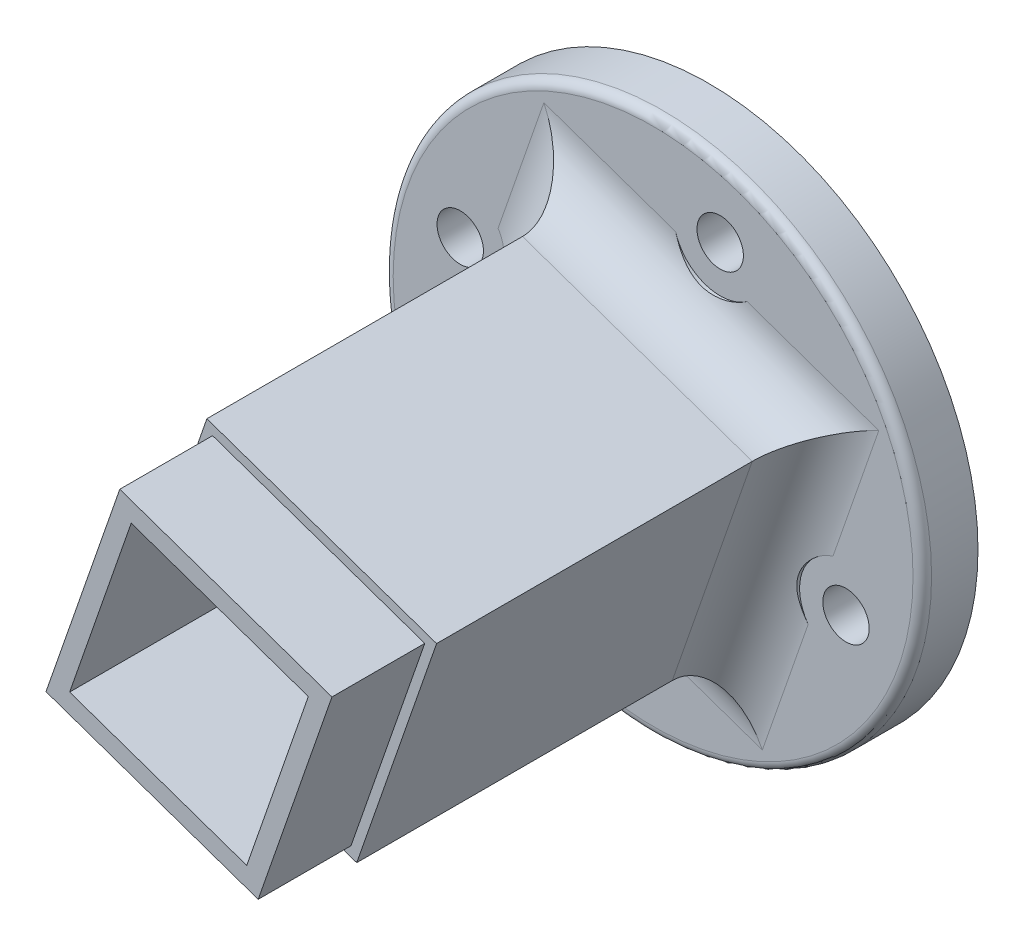
SolidWorks part; units mm, degrees
ref_plane "前视基准面" through (0, 0, 0) normal (0, 0, 1) x (1, 0, 0)
ref_plane "上视基准面" through (0, 0, 0) normal (0, 1, 0) x (1, 0, 0)
ref_plane "右视基准面" through (0, 0, 0) normal (1, 0, 0) x (0, 0, -1)
sketch "草图1" plane through (0, 0, 0) normal (0, 0, 1) x (1, 0, 0)
  line L0 (1.9417, -4.0121) -> (-2.8502, 5.8893) construction
  line L1 (1.9417, -4.0121) -> (5.5546, 6.3777) construction
  circle A0 centre (-2.8502, 5.8893) radius 1.25
  circle A1 centre (5.5546, 6.3777) radius 1.25
  circle A2 centre (11.8431, 0.7799) radius 1.25
  circle A3 centre (12.3314, -7.625) radius 1.25
  circle A4 centre (6.7336, -13.9134) radius 1.25
  circle A5 centre (-1.6712, -14.4018) radius 1.25
  circle A6 centre (-7.9597, -8.804) radius 1.25
  circle A7 centre (-8.448, -0.3991) radius 1.25
  circle A8 centre (1.9417, -4.0121) radius 14.5
  dimension "D1" = 2.5
  dimension "D3" = 29
  dimension "D2" = 45
extrude "凸台-拉伸1" add sketch "草图1" along normal blind 3
sketch "草图2" plane through (0, 0, 3) normal (0, 0, 1) x (1, 0, 0)
  line L0 (1.9417, -4.0121) -> (0.8179, 10.4443)
  line L1 (1.9417, -4.0121) -> (6.7336, -13.9134)
  line L2 (1.9417, -4.0121) -> (6.0399, -11.4588)
  line L3 (1.9417, -4.0121) -> (-1.7612, 3.639)
  line L4 (1.9417, -4.0121) -> (-2.1565, 3.4347)
  circle A0 centre (1.9417, -4.0121) radius 8.5
  circle A1 centre (1.9417, -4.0121) radius 14.5 construction
  circle A2 centre (1.9417, -4.0121) radius 6.5
  dimension "D2" = 17
  dimension "D3" = 13
  dimension "D1" = 0
  dimension "D4" = 3
  dimension "D5" = 180
  dimension "D6" = 180
extrude "凸台-拉伸2" add sketch "草图2" along normal blind 30 contours A2 L4 A0 L1 | A2 L2 A0 L0 | A2 L0 A0 L3
fillet "圆角2" radius 0.5 3 edges at (9.4932, -0.1102, 3) (-5.6098, -7.9139, 3) (16.4417, -4.0121, 3)
ref_plane "基准面4" through (5.9459, -11.5074, 0) normal (0.459, -0.8884, 0) x (-0.8884, -0.459, 0)
sketch "草图5" plane through (5.9459, -11.5074, 0) normal (0.459, -0.8884, 0) x (-0.8884, -0.459, 0)
  line L0 (0.3392, -3.5) -> (8.6167, -3.5) construction
  line L1 (0.3392, -33) -> (2.3392, -33)
  line L2 (0.3392, -33) -> (0.3392, -6.5)
  line L3 (0.3392, -6.5) -> (2.3392, -6.5)
  line L4 (2.3392, -33) -> (2.3392, -6.5)
  line L5 (-0.1058, -3.5) -> (-8.3833, -3.5) construction
  line L6 (-0.1058, -33) -> (-2.1058, -33)
  line L7 (-0.1058, -33) -> (-0.1058, -6.5)
  line L8 (-0.1058, -6.5) -> (-2.1058, -6.5)
  line L9 (-2.1058, -33) -> (-2.1058, -6.5)
  dimension "D1" = 3
  dimension "D2" = 3
  dimension "D3" = 2
  dimension "D4" = 2
extrude "凸台-拉伸4" add sketch "草图5" along normal blind 5 and the other way blind 1
fillet "圆角4" radius 2 2 edges at (3.7333, -12.3211, 19.75) (7.6823, -10.2806, 19.75)
fillet "圆角5" radius 2 2 edges at (4.1014, -12.2331, 6.5) (7.3976, -10.53, 6.5)
ref_plane "基准面5" through (-1.8552, 3.5904, 0) normal (-0.459, 0.8884, 0) x (0.8884, 0.459, 0)
sketch "草图6" plane through (-1.8552, 3.5904, 0) normal (-0.459, 0.8884, 0) x (0.8884, 0.459, 0)
  line L1 (-0.3392, -33) -> (-2.3392, -33)
  line L2 (-0.3392, -33) -> (-0.3392, -6.5)
  line L3 (-0.3392, -6.5) -> (-2.3392, -6.5)
  line L4 (-2.3392, -33) -> (-2.3392, -6.5)
  line L5 (0.1058, -33) -> (2.1058, -33)
  line L6 (0.1058, -33) -> (0.1058, -6.5)
  line L7 (0.1058, -6.5) -> (2.1058, -6.5)
  line L8 (2.1058, -33) -> (2.1058, -6.5)
  line L11 (0.1058, -3.5) -> (8.3833, -3.5) construction
  line L12 (-0.3392, -3.5) -> (-8.6167, -3.5) construction
  dimension "D1" = 2
  dimension "D2" = 2
  dimension "D3" = 3
  dimension "D4" = 3
extrude "凸台-拉伸5" add sketch "草图6" along normal blind 5 and the other way blind 1
fillet "圆角6" radius 2 4 edges at (-3.7989, 2.2565, 19.75) (0.1501, 4.297, 19.75) (-3.0129, 2.8946, 6.5) (-0.8252, 4.025, 6.5)
sketch "草图7" plane through (-2.0782, -1.0738, 0) normal (-0.8884, -0.459, 0) x (0, 0, 1)
  line L0 (6.5, 9.0414) -> (33, 9.0414) construction
  line L1 (33, 5.1579) -> (33, 9.0414) construction
  line L2 (6.5, 5.8064) -> (6.5, 9.0414) construction
  line L3 (33, -14.0692) -> (33, -17.9528) construction
  line L5 (33, -17.9528) -> (6.5, -17.9528) construction
  line L6 (6.5, -14.7178) -> (6.5, -17.9528) construction
  circle A0 centre (30, 7.0414) radius 1
  circle A1 centre (9.5, 7.0414) radius 1
  circle A2 centre (20, 7.0414) radius 1
  circle A3 centre (30, -15.9528) radius 1
  circle A4 centre (9.5, -15.9528) radius 1
  circle A5 centre (20, -15.9528) radius 1
  dimension "D2" = 2
  dimension "D4" = 2
  dimension "D7" = 2
  dimension "D9" = 2
  dimension "D12" = 2
  dimension "D15" = 2
  dimension "D1" = 2
  dimension "D3" = 3
  dimension "D5" = 2
  dimension "D6" = 3
  dimension "D8" = 10
  dimension "D10" = 3
  dimension "D11" = 2
  dimension "D13" = 2
  dimension "D14" = 3
  dimension "D16" = 10
extrude "切除-拉伸2" cut sketch "草图7" against normal blind 5
ref_plane "基准面6" through (5.0756, -9.7067, 33) normal (0.8761, 0.4821, 0) x (0, 0, -1)
ref_plane "基准面7" through (0, 0, 3) normal (0, 0, 1) x (1, 0, 0)
sketch "草图9" plane through (0, 0, 3) normal (0, 0, 1) x (1, 0, 0)
  circle A0 centre (1.9417, -4.0121) radius 7
  dimension "D1" = 14
extrude "切除-拉伸3" cut sketch "草图9" along normal blind 30
sketch "草图12" plane through (0, 0, 33) normal (0, 0, 1) x (1, 0, 0)
  line L5 (-4.4207, -7.3019) -> (4.9076, -10.1404)
  line L6 (5.4619, -10.0625) -> (8.3041, -0.7222)
  line L7 (8.3041, -0.7222) -> (-1.0242, 2.1163)
  line L8 (-1.5785, 2.0384) -> (-4.4207, -7.3019)
  line L10 (4.9911, -10.3129) -> (4.9076, -10.1404)
  line L11 (-1.1077, 2.2888) -> (-1.0242, 2.1163)
  arc A2 (-1.4333, 2.1206) -> (4.9911, -10.3129) centre (1.9417, -4.0121) ccw construction
  arc A3 (5.3167, -10.1447) -> (-1.1077, 2.2888) centre (1.9417, -4.0121) ccw construction
  arc A4 (-1.4333, 2.1206) -> (4.9911, -10.3129) centre (1.9417, -4.0121) ccw
  arc A5 (5.4619, -10.0625) -> (-1.1077, 2.2888) centre (1.9417, -4.0121) ccw
  arc M2 (4.9911, -10.3129) -> (-1.4333, 2.1206) centre (1.9417, -4.0121) cw
extrude "凸台-拉伸8" add sketch "草图12" against normal blind 32 contours L8 M2 | L7 A5 L11 | L6 A5 | L10 L5 M2
sketch "草图13" plane through (0, 0, 33) normal (0, 0, 1) x (1, 0, 0)
  line L0 (8.0844, -0.6554) -> (8.3041, -0.7222)
  line L1 (8.2354, -0.9479) -> (8.3041, -0.7222)
  line L2 (8.0844, -0.6554) -> (-1.0242, 2.1163) construction
  line L3 (5.4619, -10.0625) -> (8.2354, -0.9479) construction
  line L4 (8.0844, -0.6554) -> (8.2354, -0.9479)
  arc A0 (8.2354, -0.9479) -> (8.0844, -0.6554) centre (1.9417, -4.0121) ccw construction
  arc A1 (8.2354, -0.9479) -> (8.0844, -0.6554) centre (1.9417, -4.0121) ccw construction
  dimension "D1" = 180
  dimension "D2" = 180
extrude "切除-拉伸4" cut sketch "草图13" against normal blind 30
sketch "草图14" plane through (0, 0, 33) normal (0, 0, 1) x (1, 0, 0)
  line L0 (-1.5785, 2.0384) -> (-1.5147, 2.2686)
  line L1 (18.9657, -34.9461) -> (-8.8145, 15.5328) construction
  line L2 (-1.5785, 2.0384) -> (-1.4333, 2.1206)
  line L3 (-1.5147, 2.2686) -> (-1.4333, 2.1206)
  arc A0 (-1.4333, 2.1206) -> (-1.5785, 2.0384) centre (1.9417, -4.0121) ccw construction
  dimension "D1" = 45
extrude "切除-拉伸5" cut sketch "草图14" against normal blind 30 contours L3 L2 L0
sketch "草图15" plane through (0, 0, 33) normal (0, 0, 1) x (1, 0, 0)
  line L0 (-4.352, -7.0762) -> (-4.4207, -7.3019)
  line L1 (-4.4207, -7.3019) -> (-4.201, -7.3687)
  line L2 (-1.5785, 2.0384) -> (-4.352, -7.0762) construction
  line L3 (-4.201, -7.3687) -> (4.9076, -10.1404) construction
  line L4 (-4.352, -7.0762) -> (-4.201, -7.3687)
  dimension "D1" = 180
  dimension "D2" = 180
extrude "切除-拉伸6" cut sketch "草图15" against normal blind 30
sketch "草图16" plane through (0, 0, 33) normal (0, 0, 1) x (1, 0, 0)
  line L0 (5.4619, -10.0625) -> (5.3981, -10.2927)
  line L1 (18.9657, -34.9461) -> (-8.8145, 15.5328) construction
  line L2 (5.4619, -10.0625) -> (5.3167, -10.1447)
  line L3 (5.3167, -10.1447) -> (5.3981, -10.2927)
  arc A0 (5.3167, -10.1447) -> (5.4619, -10.0625) centre (1.9417, -4.0121) ccw construction
  arc A1 (5.3167, -10.1447) -> (5.4619, -10.0625) centre (1.9417, -4.0121) ccw construction
  dimension "D1" = 45
extrude "切除-拉伸7" cut sketch "草图16" against normal blind 30
sketch "草图17" plane through (0, 0, 33) normal (0, 0, 1) x (1, 0, 0)
  line L0 (-1.5147, 2.2686) -> (-4.4207, -7.3019)
  line L1 (-2.0647, 0.01) -> (-3.8637, -5.9148)
  line L2 (-3.8637, -5.9148) -> (-4.2963, -7.3397)
  line L3 (-1.5785, 2.0384) -> (-1.5147, 2.2686) construction
  line L4 (-1.5785, 2.0384) -> (-1.5147, 2.2686) construction
  line L5 (-4.4207, -7.3019) -> (-4.2963, -7.3397)
  line L6 (-4.4207, -7.3019) -> (4.9076, -10.1404) construction
  line L7 (-2.0647, 0.01) -> (-1.4272, 2.1095)
  line L8 (-1.5147, 2.2686) -> (-1.4272, 2.1095)
  line L9 (18.9657, -34.9461) -> (-8.8145, 15.5328) construction
  dimension "D1" = 0.13
  dimension "D2" = 180
  dimension "D3" = 180
extrude "凸台-拉伸9" add sketch "草图17" against normal blind 30
sketch "草图19" plane through (0, 0, 33) normal (0, 0, 1) x (1, 0, 0)
  line L0 (-1.4232, 2.1023) -> (-4.2963, -7.3397)
  line L1 (18.9657, -34.9461) -> (-8.8145, 15.5328) construction
  line L2 (-4.2963, -7.3397) -> (4.9076, -10.1404)
  line L3 (-1.4232, 2.1023) -> (-1.4272, 2.1095)
  line L4 (-4.2963, -7.3397) -> (-1.4272, 2.1095) construction
  line L5 (-1.4272, 2.1095) -> (-4.6964, -7.7435)
  line L6 (-4.6964, -7.7435) -> (4.9076, -10.1404)
  dimension "D1" = 90
extrude "凸台-拉伸11" add sketch "草图19" against normal blind 30
sketch "草图20" plane through (0, 0, 33) normal (0, 0, 1) x (1, 0, 0)
  line L0 (-1.0242, 2.1163) -> (8.3041, -0.7222)
  line L1 (8.3041, -0.7222) -> (5.3941, -10.2854)
  line L2 (18.9657, -34.9461) -> (-8.8145, 15.5328) construction
  line L3 (5.3981, -10.2927) -> (6.0399, -11.4588) construction
  line L4 (5.3941, -10.2854) -> (5.4317, -10.3537)
  line L5 (5.4317, -10.3537) -> (8.9463, -0.477)
  line L6 (8.9463, -0.477) -> (-1.0242, 2.1163)
  dimension "D1" = 90
extrude "凸台-拉伸12" add sketch "草图20" against normal blind 30
sketch "草图21" plane through (0, 0, 33) normal (0, 0, 1) x (1, 0, 0)
  line L7 (-7.9597, -8.804) -> (11.8431, 0.7799)
  line L8 (-2.8502, 5.8893) -> (6.7336, -13.9134)
  circle A0 centre (-2.8502, 5.8893) radius 1.25 construction
  circle A1 centre (6.7336, -13.9134) radius 1.25 construction
  circle A2 centre (11.8431, 0.7799) radius 1.25 construction
  circle A3 centre (-7.9597, -8.804) radius 1.25 construction
  circle A4 centre (-2.8502, 5.8893) radius 1.25
  circle A5 centre (6.7336, -13.9134) radius 1.25
  circle A6 centre (11.8431, 0.7799) radius 1.25
  circle A7 centre (-7.9597, -8.804) radius 1.25
  circle A8 centre (1.9417, -4.0121) radius 8
  line M9 (-1.0242, 2.1163) -> (8.3041, -0.7222)
  line M10 (8.3041, -0.7222) -> (5.3941, -10.2854)
  line M11 (5.3941, -10.2854) -> (6.0399, -11.4588)
extrude "凸台-拉伸13" add sketch "草图21" against normal blind 30 contours L8 L7 M9 M10 | L8 A8 L7 M11 M10 | L7 A8 L8 | L8 A8 L7
sketch "草图22" plane through (0, 0, 33) normal (0, 0, 1) x (1, 0, 0)
  line L0 (-2.8502, 5.8893) -> (6.7336, -13.9134)
  line L1 (11.8431, 0.7799) -> (-7.9597, -8.804)
  line L2 (-1.1382, 2.3518) -> (-4.4222, -7.092)
  line L3 (-4.4222, -7.092) -> (5.0216, -10.3759)
  line L4 (5.0216, -10.3759) -> (8.3056, -0.9322)
  line L5 (8.3056, -0.9322) -> (-1.1382, 2.3518)
  line L16 (-1.9154, 2.9967) -> (-2.1565, 3.4347)
  line L20 (4.3802, -13.5731) -> (6.1629, -17.0233)
  line L21 (6.1629, -17.0233) -> (7.9398, -16.1052)
  line L22 (7.9398, -16.1052) -> (5.6445, -11.6631)
  line L23 (5.6445, -11.6631) -> (5.4267, -11.2131)
  line L24 (5.7988, -11.0208) -> (6.0399, -11.4588)
  line L25 (6.0399, -11.4588) -> (8.3351, -15.9009)
  line L26 (8.3351, -15.9009) -> (10.1119, -14.9828)
  line L27 (10.1119, -14.9828) -> (8.3292, -11.5326)
  line L31 (-1.7612, 3.639) -> (-1.5433, 3.189)
  line L32 (-1.9154, 2.9967) -> (-2.1565, 3.4347)
  line L36 (4.3802, -13.5731) -> (6.1629, -17.0233)
  line L37 (6.1629, -17.0233) -> (7.9398, -16.1052)
  line L38 (7.9398, -16.1052) -> (5.6445, -11.6631)
  line L39 (5.6445, -11.6631) -> (5.4267, -11.2131)
  line L40 (5.7988, -11.0208) -> (6.0399, -11.4588)
  line L41 (6.0399, -11.4588) -> (8.3351, -15.9009)
  line L42 (8.3351, -15.9009) -> (10.1119, -14.9828)
  line L43 (10.1119, -14.9828) -> (8.3292, -11.5326)
  line L47 (-1.7612, 3.639) -> (-1.5433, 3.189)
  line L48 (-2.1565, 3.4347) -> (-4.4517, 7.8768)
  line L49 (-2.1565, 3.4347) -> (-4.4517, 7.8768)
  line L50 (-4.4517, 7.8768) -> (-6.2286, 6.9587)
  line L51 (-4.4517, 7.8768) -> (-6.2286, 6.9587)
  line L52 (-6.2286, 6.9587) -> (-4.4458, 3.5085)
  line L53 (-6.2286, 6.9587) -> (-4.4458, 3.5085)
  line L54 (-0.4968, 5.549) -> (-2.2795, 8.9992)
  line L55 (-0.4968, 5.549) -> (-2.2795, 8.9992)
  line L56 (-2.2795, 8.9992) -> (-4.0564, 8.0811)
  line L57 (-2.2795, 8.9992) -> (-4.0564, 8.0811)
  line L58 (-4.0564, 8.0811) -> (-1.7612, 3.639)
  line L59 (-4.0564, 8.0811) -> (-1.7612, 3.639)
  circle A0 centre (11.8431, 0.7799) radius 1.25 construction
  circle A1 centre (11.8431, 0.7799) radius 1.25
  circle A2 centre (-2.8502, 5.8893) radius 1.25 construction
  circle A3 centre (6.7336, -13.9134) radius 1.25 construction
  circle A4 centre (-7.9597, -8.804) radius 1.25 construction
  circle A5 centre (-2.8502, 5.8893) radius 1.25
  circle A6 centre (6.7336, -13.9134) radius 1.25
  circle A7 centre (-7.9597, -8.804) radius 1.25
  arc A8 (-1.5433, 3.189) -> (-1.9154, 2.9967) centre (1.9417, -4.0121) ccw
  arc A10 (-4.6676, 1.3328) -> (2.4774, -12.4952) centre (1.9417, -4.0121) ccw
  arc A11 (4.3802, -13.5731) -> (2.4774, -12.4952) centre (2.6034, -14.4912) ccw
  arc A12 (5.4267, -11.2131) -> (5.7988, -11.0208) centre (1.9417, -4.0121) ccw
  arc A13 (8.5509, -9.3569) -> (8.3292, -11.5326) centre (10.1061, -10.6146) ccw
  arc A14 (8.5509, -9.3569) -> (1.406, 4.4711) centre (1.9417, -4.0121) ccw
  arc A16 (-1.5433, 3.189) -> (-1.9154, 2.9967) centre (1.9417, -4.0121) ccw
  arc A18 (-4.6676, 1.3328) -> (2.4774, -12.4952) centre (1.9417, -4.0121) ccw
  arc A19 (4.3802, -13.5731) -> (2.4774, -12.4952) centre (2.6034, -14.4912) ccw
  arc A20 (5.4267, -11.2131) -> (5.7988, -11.0208) centre (1.9417, -4.0121) ccw
  arc A21 (8.5509, -9.3569) -> (8.3292, -11.5326) centre (10.1061, -10.6146) ccw
  arc A22 (8.5509, -9.3569) -> (1.406, 4.4711) centre (1.9417, -4.0121) ccw
  circle A24 centre (1.9417, -4.0121) radius 7.07
  arc A31 (-4.6676, 1.3328) -> (-4.4458, 3.5085) centre (-6.2227, 2.5905) ccw
  arc A32 (-4.6676, 1.3328) -> (-4.4458, 3.5085) centre (-6.2227, 2.5905) ccw
  arc A33 (-0.4968, 5.549) -> (1.406, 4.4711) centre (1.28, 6.4671) ccw
  arc A34 (-0.4968, 5.549) -> (1.406, 4.4711) centre (1.28, 6.4671) ccw
  dimension "D1" = 0
extrude "切除-拉伸8" cut sketch "草图22" against normal blind 30 contours L1 L5 L0 | L0 L4 L1 | L1 L3 L0 | L0 L2 L1
sketch "草图24" plane through (0, 0, 33) normal (0, 0, 1) x (1, 0, 0)
  line L0 (8.3351, -15.9009) -> (-4.0564, 8.0811)
  line L1 (-4.0564, 8.0811) -> (-4.4517, 7.8768)
  line L2 (-4.4517, 7.8768) -> (7.9398, -16.1052)
  line L3 (7.9398, -16.1052) -> (8.3351, -15.9009)
extrude "切除-拉伸15" cut sketch "草图24" against normal blind 30
sketch "草图25" plane through (0, 0, 33) normal (0, 0, 1) x (1, 0, 0)
  line L1 (-18.986, 14.7091) -> (22.8694, 14.7091)
  line L2 (-18.986, 14.7091) -> (-18.986, -22.7332)
  line L3 (-18.986, -22.7332) -> (22.8694, -22.7332)
  line L4 (22.8694, 14.7091) -> (22.8694, -22.7332)
  line L5 (-18.986, 14.7091) -> (22.8694, -22.7332) construction
  line L6 (-18.986, -22.7332) -> (22.8694, 14.7091) construction
  point P0 (1.9417, -4.0121)
extrude "切除-拉伸16" cut sketch "草图25" against normal up to surface (30 mm away) up to face at (-0.2298, -5.1601, 3)
sketch "草图26" plane through (0, 0, 3) normal (0, 0, 1) x (1, 0, 0)
  line L0 (-8.448, -0.3991) -> (12.3314, -7.625)
  line L1 (5.5546, 6.3777) -> (-1.6712, -14.4018)
  line L2 (-1.1695, 2.4164) -> (8.3702, -0.9009)
  line L3 (5.0529, -10.4406) -> (8.3702, -0.9009)
  line L4 (-4.4868, -7.1232) -> (5.0529, -10.4406)
  line L5 (-4.4868, -7.1232) -> (-1.1695, 2.4164)
  line L6 (5.977, -12.35) -> (10.2796, 0.0232)
  line L7 (-2.0936, 4.3259) -> (10.2796, 0.0232)
  line L8 (-6.3963, -8.0473) -> (-2.0936, 4.3259)
  line L9 (-6.3963, -8.0473) -> (5.977, -12.35)
  point P12 (6.7115, -5.6707)
  point P15 (0.283, -8.7819)
  point P16 (3.6004, 0.7578)
  dimension "D1" = 5.05
  dimension "D2" = 5.05
  dimension "D3" = 1.5
extrude "凸台-拉伸14" add sketch "草图26" along normal blind 20 contours L8 L0 L5 L2 L1 L7 | L7 L1 L2 L3 L0 L6 | L1 L9 L6 L0 L3 L4 | L8 L9 L1 L4 L5 L0
sketch "草图27" plane through (0, 0, 0) normal (0, 0, -1) x (-1, 0, 0)
  circle A0 centre (7.9597, -8.804) radius 1.25 construction
  circle A1 centre (-1.9417, -4.0121) radius 14.5
  circle A2 centre (-1.9417, -4.0121) radius 14.5
  circle A3 centre (2.8502, 5.8893) radius 1.25 construction
  circle A4 centre (-11.8431, 0.7799) radius 1.25 construction
  circle A5 centre (-6.7336, -13.9134) radius 1.25 construction
  circle A6 centre (-6.7336, -13.9134) radius 1.25
  circle A7 centre (-11.8431, 0.7799) radius 1.25
  circle A8 centre (2.8502, 5.8893) radius 1.25
  circle A9 centre (7.9597, -8.804) radius 1.25
  dimension "D1" = 0
extrude "凸台-拉伸15" add sketch "草图27" against normal up to surface (3 mm away) contours A8 | A9 | A6 | A7 up to face at (-7.198, -0.3991, 3)
fillet "圆角8" radius 3 4 edges at (-4.2449, -1.8607, 3) (8.1283, -6.1634, 3) (4.093, 2.1746, 3) (-0.2096, -10.1987, 3)
sketch "草图28" plane through (0, 0, 3) normal (0, 0, 1) x (1, 0, 0)
  circle A0 centre (-8.448, -0.3991) radius 2.5
  circle A1 centre (5.5546, 6.3777) radius 2.5
  circle A2 centre (12.3314, -7.625) radius 2.5
  circle A3 centre (-1.6712, -14.4018) radius 2.5
  point P12 (1.9417, -4.0121)
  dimension "D1" = 5
  dimension "D2" = 4
extrude "切除-拉伸17" cut sketch "草图28" along normal blind 20
sketch "草图29" plane through (0, 0, 23) normal (0, 0, 1) x (1, 0, 0)
  line L4 (-6.3963, -8.0473) -> (5.977, -12.35)
  line L5 (5.977, -12.35) -> (10.2796, 0.0232)
  line L6 (10.2796, 0.0232) -> (-2.0936, 4.3259)
  line L7 (-2.0936, 4.3259) -> (-6.3963, -8.0473)
  line L8 (-6.3963, -8.0473) -> (5.977, -12.35)
  line L9 (5.977, -12.35) -> (10.2796, 0.0232)
  line L10 (10.2796, 0.0232) -> (-2.0936, 4.3259)
  line L11 (-2.0936, 4.3259) -> (-6.3963, -8.0473)
  line L15 (-5.7598, -7.7393) -> (5.6689, -11.7135)
  line L16 (5.6689, -11.7135) -> (9.6432, -0.2848)
  line L17 (9.6432, -0.2848) -> (-1.7855, 3.6894)
  line L18 (-1.7855, 3.6894) -> (-5.7598, -7.7393)
  line L19 (-4.4868, -7.1232) -> (5.0529, -10.4406) construction
  line L20 (5.0529, -10.4406) -> (8.3702, -0.9009) construction
  line L21 (-1.1695, 2.4164) -> (8.3702, -0.9009) construction
  line L22 (-4.4868, -7.1232) -> (-1.1695, 2.4164) construction
  line L23 (-4.4868, -7.1232) -> (5.0529, -10.4406)
  line L24 (5.0529, -10.4406) -> (8.3702, -0.9009)
  line L25 (-1.1695, 2.4164) -> (8.3702, -0.9009)
  line L26 (-4.4868, -7.1232) -> (-1.1695, 2.4164)
  line M17 (8.3702, -0.9009) -> (5.0529, -10.4406)
  line M18 (5.0529, -10.4406) -> (-4.4868, -7.1232)
  line M19 (-4.4868, -7.1232) -> (-1.1695, 2.4164)
  line M20 (-1.1695, 2.4164) -> (8.3702, -0.9009)
  dimension "D1" = 0
  dimension "D2" = 0.5
extrude "凸台-拉伸16" add sketch "草图29" along normal blind 5 contours L17 L18 L15 L16 M20 M17 M18 M19
